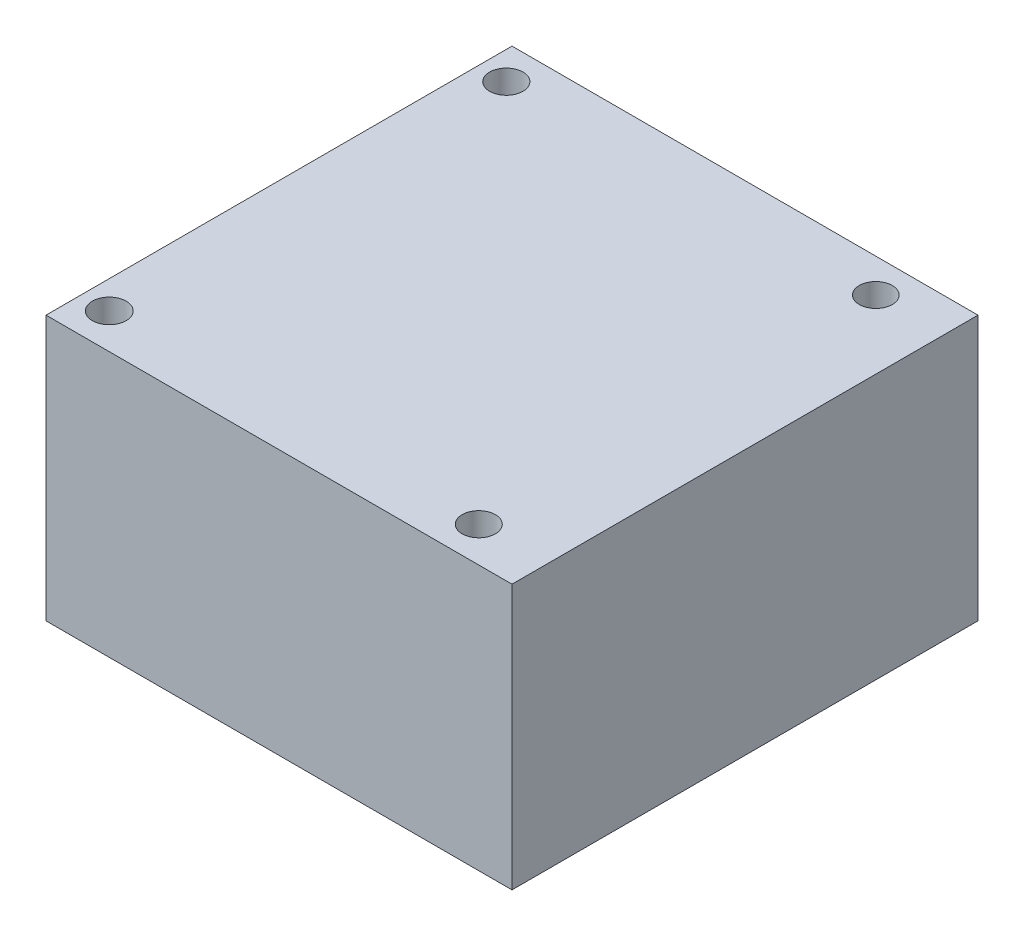
SolidWorks part; units mm, degrees
ref_plane "Płaszczyzna przednia" through (0, 0, 0) normal (0, 0, 1) x (1, 0, 0)
ref_plane "Płaszczyzna górna" through (0, 0, 0) normal (0, 1, 0) x (1, 0, 0)
ref_plane "Płaszczyzna prawa" through (0, 0, 0) normal (1, 0, 0) x (0, 0, -1)
sketch "Sketch1" plane through (0, 0, 0) normal (0, 1, 0) x (1, 0, 0)
  line L1 (-22, -27.726) -> (22, -27.726)
  line L2 (-22, -27.726) -> (-22, 16.274)
  line L3 (-22, 16.274) -> (22, 16.274)
  line L4 (22, -27.726) -> (22, 16.274)
  dimension "D1" = 44
  dimension "D2" = 44
extrude "Boss-Extrude1" add sketch "Sketch1" along normal blind 25
sketch "Sketch2" plane through (0, 25, 0) normal (0, 1, 0) x (1, 0, 0)
  circle A0 centre (15.5286, 13.094) radius 1.559
  circle A1 centre (15.5286, -24.3922) radius 1.5711
  circle A2 centre (-19.3584, -24.3922) radius 1.5983
  circle A3 centre (-19.3584, 13.094) radius 1.5752
extrude "Cut-Extrude1" cut sketch "Sketch2" against normal blind 30
